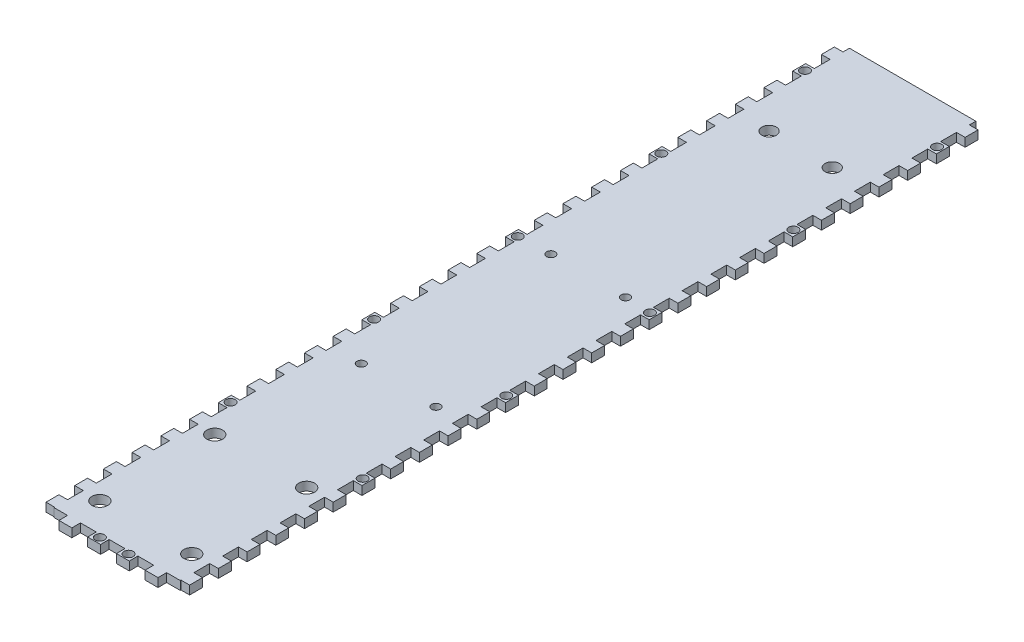
SolidWorks part; units mm, degrees
ref_plane "Plan de face" through (0, 0, 0) normal (0, 0, 1) x (1, 0, 0)
ref_plane "Plan de dessus" through (0, 0, 0) normal (0, 1, 0) x (1, 0, 0)
ref_plane "Plan de droite" through (0, 0, 0) normal (1, 0, 0) x (0, 0, -1)
sketch "Sketch1" plane through (0, 0, 0) normal (0, 0, 1) x (1, 0, 0)
  line L1 (-30.0201, 10.5217) -> (13.9799, 10.5217)
  line L2 (-30.0201, 10.5217) -> (-30.0201, 7.5217)
  line L3 (-30.0201, 7.5217) -> (13.9799, 7.5217)
  line L4 (13.9799, 10.5217) -> (13.9799, 7.5217)
  dimension "D1" = 44
  dimension "D2" = 3
extrude "Boss-Extrude1" add sketch "Sketch1" along normal blind 277
sketch "Sketch4" plane through (13.9799, 0, 0) normal (1, 0, 0) x (0, 0, -1)
  line L0 (-277, 10.5217) -> (0, 10.5217) construction
  line L1 (-276.75, 10.5217) -> (-272.25, 10.5217)
  line L2 (-276.75, 10.5217) -> (-276.75, 7.5217)
  line L3 (-276.75, 7.5217) -> (-272.25, 7.5217)
  line L4 (-272.25, 10.5217) -> (-272.25, 7.5217)
  line L5 (-277, 7.5217) -> (0, 7.5217) construction
  line L6 (-277, 7.5217) -> (-277, 10.5217) construction
  line L7 (-266.75, 10.5217) -> (-266.75, 7.5217)
  line L8 (-266.75, 10.5217) -> (-262.25, 10.5217)
  line L9 (-262.25, 10.5217) -> (-262.25, 7.5217)
  line L10 (-266.75, 7.5217) -> (-262.25, 7.5217)
  line L11 (-256.75, 10.5217) -> (-256.75, 7.5217)
  line L12 (-256.75, 10.5217) -> (-252.25, 10.5217)
  line L13 (-252.25, 10.5217) -> (-252.25, 7.5217)
  line L14 (-256.75, 7.5217) -> (-252.25, 7.5217)
  line L15 (-246.75, 10.5217) -> (-246.75, 7.5217)
  line L16 (-246.75, 10.5217) -> (-242.25, 10.5217)
  line L17 (-242.25, 10.5217) -> (-242.25, 7.5217)
  line L18 (-246.75, 7.5217) -> (-242.25, 7.5217)
  line L19 (-236.75, 10.5217) -> (-236.75, 7.5217)
  line L20 (-236.75, 10.5217) -> (-232.25, 10.5217)
  line L21 (-232.25, 10.5217) -> (-232.25, 7.5217)
  line L22 (-236.75, 7.5217) -> (-232.25, 7.5217)
  line L23 (-226.75, 10.5217) -> (-226.75, 7.5217)
  line L24 (-226.75, 10.5217) -> (-222.25, 10.5217)
  line L25 (-222.25, 10.5217) -> (-222.25, 7.5217)
  line L26 (-226.75, 7.5217) -> (-222.25, 7.5217)
  line L27 (-216.75, 10.5217) -> (-216.75, 7.5217)
  line L28 (-216.75, 10.5217) -> (-212.25, 10.5217)
  line L29 (-212.25, 10.5217) -> (-212.25, 7.5217)
  line L30 (-216.75, 7.5217) -> (-212.25, 7.5217)
  line L31 (-206.75, 10.5217) -> (-206.75, 7.5217)
  line L32 (-206.75, 10.5217) -> (-202.25, 10.5217)
  line L33 (-202.25, 10.5217) -> (-202.25, 7.5217)
  line L34 (-206.75, 7.5217) -> (-202.25, 7.5217)
  line L35 (-196.75, 10.5217) -> (-196.75, 7.5217)
  line L36 (-196.75, 10.5217) -> (-192.25, 10.5217)
  line L37 (-192.25, 10.5217) -> (-192.25, 7.5217)
  line L38 (-196.75, 7.5217) -> (-192.25, 7.5217)
  line L39 (-186.75, 10.5217) -> (-186.75, 7.5217)
  line L40 (-186.75, 10.5217) -> (-182.25, 10.5217)
  line L41 (-182.25, 10.5217) -> (-182.25, 7.5217)
  line L42 (-186.75, 7.5217) -> (-182.25, 7.5217)
  line L43 (-176.75, 10.5217) -> (-176.75, 7.5217)
  line L44 (-176.75, 10.5217) -> (-172.25, 10.5217)
  line L45 (-172.25, 10.5217) -> (-172.25, 7.5217)
  line L46 (-176.75, 7.5217) -> (-172.25, 7.5217)
  line L47 (-166.75, 10.5217) -> (-166.75, 7.5217)
  line L48 (-166.75, 10.5217) -> (-162.25, 10.5217)
  line L49 (-162.25, 10.5217) -> (-162.25, 7.5217)
  line L50 (-166.75, 7.5217) -> (-162.25, 7.5217)
  line L51 (-156.75, 10.5217) -> (-156.75, 7.5217)
  line L52 (-156.75, 10.5217) -> (-152.25, 10.5217)
  line L53 (-152.25, 10.5217) -> (-152.25, 7.5217)
  line L54 (-156.75, 7.5217) -> (-152.25, 7.5217)
  line L55 (-146.75, 10.5217) -> (-146.75, 7.5217)
  line L56 (-146.75, 10.5217) -> (-142.25, 10.5217)
  line L57 (-142.25, 10.5217) -> (-142.25, 7.5217)
  line L58 (-146.75, 7.5217) -> (-142.25, 7.5217)
  line L59 (-136.75, 10.5217) -> (-136.75, 7.5217)
  line L60 (-136.75, 10.5217) -> (-132.25, 10.5217)
  line L61 (-132.25, 10.5217) -> (-132.25, 7.5217)
  line L62 (-136.75, 7.5217) -> (-132.25, 7.5217)
  line L63 (-126.75, 10.5217) -> (-126.75, 7.5217)
  line L64 (-126.75, 10.5217) -> (-122.25, 10.5217)
  line L65 (-122.25, 10.5217) -> (-122.25, 7.5217)
  line L66 (-126.75, 7.5217) -> (-122.25, 7.5217)
  line L67 (-116.75, 10.5217) -> (-116.75, 7.5217)
  line L68 (-116.75, 10.5217) -> (-112.25, 10.5217)
  line L69 (-112.25, 10.5217) -> (-112.25, 7.5217)
  line L70 (-116.75, 7.5217) -> (-112.25, 7.5217)
  line L71 (-106.75, 10.5217) -> (-106.75, 7.5217)
  line L72 (-106.75, 10.5217) -> (-102.25, 10.5217)
  line L73 (-102.25, 10.5217) -> (-102.25, 7.5217)
  line L74 (-106.75, 7.5217) -> (-102.25, 7.5217)
  line L75 (-96.75, 10.5217) -> (-96.75, 7.5217)
  line L76 (-96.75, 10.5217) -> (-92.25, 10.5217)
  line L77 (-92.25, 10.5217) -> (-92.25, 7.5217)
  line L78 (-96.75, 7.5217) -> (-92.25, 7.5217)
  line L79 (-86.75, 10.5217) -> (-86.75, 7.5217)
  line L80 (-86.75, 10.5217) -> (-82.25, 10.5217)
  line L81 (-82.25, 10.5217) -> (-82.25, 7.5217)
  line L82 (-86.75, 7.5217) -> (-82.25, 7.5217)
  line L83 (-76.75, 10.5217) -> (-76.75, 7.5217)
  line L84 (-76.75, 10.5217) -> (-72.25, 10.5217)
  line L85 (-72.25, 10.5217) -> (-72.25, 7.5217)
  line L86 (-76.75, 7.5217) -> (-72.25, 7.5217)
  line L87 (-66.75, 10.5217) -> (-66.75, 7.5217)
  line L88 (-66.75, 10.5217) -> (-62.25, 10.5217)
  line L89 (-62.25, 10.5217) -> (-62.25, 7.5217)
  line L90 (-66.75, 7.5217) -> (-62.25, 7.5217)
  line L91 (-56.75, 10.5217) -> (-56.75, 7.5217)
  line L92 (-56.75, 10.5217) -> (-52.25, 10.5217)
  line L93 (-52.25, 10.5217) -> (-52.25, 7.5217)
  line L94 (-56.75, 7.5217) -> (-52.25, 7.5217)
  line L95 (-46.75, 10.5217) -> (-46.75, 7.5217)
  line L96 (-46.75, 10.5217) -> (-42.25, 10.5217)
  line L97 (-42.25, 10.5217) -> (-42.25, 7.5217)
  line L98 (-46.75, 7.5217) -> (-42.25, 7.5217)
  line L99 (-36.75, 10.5217) -> (-36.75, 7.5217)
  line L100 (-36.75, 10.5217) -> (-32.25, 10.5217)
  line L101 (-32.25, 10.5217) -> (-32.25, 7.5217)
  line L102 (-36.75, 7.5217) -> (-32.25, 7.5217)
  line L103 (-26.75, 10.5217) -> (-26.75, 7.5217)
  line L104 (-26.75, 10.5217) -> (-22.25, 10.5217)
  line L105 (-22.25, 10.5217) -> (-22.25, 7.5217)
  line L106 (-26.75, 7.5217) -> (-22.25, 7.5217)
  line L107 (-16.75, 10.5217) -> (-16.75, 7.5217)
  line L108 (-16.75, 10.5217) -> (-12.25, 10.5217)
  line L109 (-12.25, 10.5217) -> (-12.25, 7.5217)
  line L110 (-16.75, 7.5217) -> (-12.25, 7.5217)
  line L111 (-6.75, 10.5217) -> (-6.75, 7.5217)
  line L112 (-6.75, 10.5217) -> (-2.25, 10.5217)
  line L113 (-2.25, 10.5217) -> (-2.25, 7.5217)
  line L114 (-6.75, 7.5217) -> (-2.25, 7.5217)
  dimension "D1" = 0.25
  dimension "D2" = 4.5
  dimension "D3" = 28
extrude "Boss-Extrude2" add sketch "Sketch4" along normal blind 3
sketch "Sketch5" plane through (-30.0201, 0, 0) normal (-1, 0, 0) x (0, 0, 1)
  line L0 (277, 7.5217) -> (0, 7.5217) construction
  line L1 (276.75, 7.5217) -> (272.25, 7.5217)
  line L2 (276.75, 7.5217) -> (276.75, 10.5217)
  line L3 (276.75, 10.5217) -> (272.25, 10.5217)
  line L4 (272.25, 7.5217) -> (272.25, 10.5217)
  line L5 (277, 10.5217) -> (0, 10.5217) construction
  line L6 (277, 10.5217) -> (277, 7.5217) construction
  line L7 (266.75, 7.5217) -> (266.75, 10.5217)
  line L8 (266.75, 7.5217) -> (262.25, 7.5217)
  line L9 (262.25, 7.5217) -> (262.25, 10.5217)
  line L10 (266.75, 10.5217) -> (262.25, 10.5217)
  line L11 (256.75, 7.5217) -> (256.75, 10.5217)
  line L12 (256.75, 7.5217) -> (252.25, 7.5217)
  line L13 (252.25, 7.5217) -> (252.25, 10.5217)
  line L14 (256.75, 10.5217) -> (252.25, 10.5217)
  line L15 (246.75, 7.5217) -> (246.75, 10.5217)
  line L16 (246.75, 7.5217) -> (242.25, 7.5217)
  line L17 (242.25, 7.5217) -> (242.25, 10.5217)
  line L18 (246.75, 10.5217) -> (242.25, 10.5217)
  line L19 (236.75, 7.5217) -> (236.75, 10.5217)
  line L20 (236.75, 7.5217) -> (232.25, 7.5217)
  line L21 (232.25, 7.5217) -> (232.25, 10.5217)
  line L22 (236.75, 10.5217) -> (232.25, 10.5217)
  line L23 (226.75, 7.5217) -> (226.75, 10.5217)
  line L24 (226.75, 7.5217) -> (222.25, 7.5217)
  line L25 (222.25, 7.5217) -> (222.25, 10.5217)
  line L26 (226.75, 10.5217) -> (222.25, 10.5217)
  line L27 (216.75, 7.5217) -> (216.75, 10.5217)
  line L28 (216.75, 7.5217) -> (212.25, 7.5217)
  line L29 (212.25, 7.5217) -> (212.25, 10.5217)
  line L30 (216.75, 10.5217) -> (212.25, 10.5217)
  line L31 (206.75, 7.5217) -> (206.75, 10.5217)
  line L32 (206.75, 7.5217) -> (202.25, 7.5217)
  line L33 (202.25, 7.5217) -> (202.25, 10.5217)
  line L34 (206.75, 10.5217) -> (202.25, 10.5217)
  line L35 (196.75, 7.5217) -> (196.75, 10.5217)
  line L36 (196.75, 7.5217) -> (192.25, 7.5217)
  line L37 (192.25, 7.5217) -> (192.25, 10.5217)
  line L38 (196.75, 10.5217) -> (192.25, 10.5217)
  line L39 (186.75, 7.5217) -> (186.75, 10.5217)
  line L40 (186.75, 7.5217) -> (182.25, 7.5217)
  line L41 (182.25, 7.5217) -> (182.25, 10.5217)
  line L42 (186.75, 10.5217) -> (182.25, 10.5217)
  line L43 (176.75, 7.5217) -> (176.75, 10.5217)
  line L44 (176.75, 7.5217) -> (172.25, 7.5217)
  line L45 (172.25, 7.5217) -> (172.25, 10.5217)
  line L46 (176.75, 10.5217) -> (172.25, 10.5217)
  line L47 (166.75, 7.5217) -> (166.75, 10.5217)
  line L48 (166.75, 7.5217) -> (162.25, 7.5217)
  line L49 (162.25, 7.5217) -> (162.25, 10.5217)
  line L50 (166.75, 10.5217) -> (162.25, 10.5217)
  line L51 (156.75, 7.5217) -> (156.75, 10.5217)
  line L52 (156.75, 7.5217) -> (152.25, 7.5217)
  line L53 (152.25, 7.5217) -> (152.25, 10.5217)
  line L54 (156.75, 10.5217) -> (152.25, 10.5217)
  line L55 (146.75, 7.5217) -> (146.75, 10.5217)
  line L56 (146.75, 7.5217) -> (142.25, 7.5217)
  line L57 (142.25, 7.5217) -> (142.25, 10.5217)
  line L58 (146.75, 10.5217) -> (142.25, 10.5217)
  line L59 (136.75, 7.5217) -> (136.75, 10.5217)
  line L60 (136.75, 7.5217) -> (132.25, 7.5217)
  line L61 (132.25, 7.5217) -> (132.25, 10.5217)
  line L62 (136.75, 10.5217) -> (132.25, 10.5217)
  line L63 (126.75, 7.5217) -> (126.75, 10.5217)
  line L64 (126.75, 7.5217) -> (122.25, 7.5217)
  line L65 (122.25, 7.5217) -> (122.25, 10.5217)
  line L66 (126.75, 10.5217) -> (122.25, 10.5217)
  line L67 (116.75, 7.5217) -> (116.75, 10.5217)
  line L68 (116.75, 7.5217) -> (112.25, 7.5217)
  line L69 (112.25, 7.5217) -> (112.25, 10.5217)
  line L70 (116.75, 10.5217) -> (112.25, 10.5217)
  line L71 (106.75, 7.5217) -> (106.75, 10.5217)
  line L72 (106.75, 7.5217) -> (102.25, 7.5217)
  line L73 (102.25, 7.5217) -> (102.25, 10.5217)
  line L74 (106.75, 10.5217) -> (102.25, 10.5217)
  line L75 (96.75, 7.5217) -> (96.75, 10.5217)
  line L76 (96.75, 7.5217) -> (92.25, 7.5217)
  line L77 (92.25, 7.5217) -> (92.25, 10.5217)
  line L78 (96.75, 10.5217) -> (92.25, 10.5217)
  line L79 (86.75, 7.5217) -> (86.75, 10.5217)
  line L80 (86.75, 7.5217) -> (82.25, 7.5217)
  line L81 (82.25, 7.5217) -> (82.25, 10.5217)
  line L82 (86.75, 10.5217) -> (82.25, 10.5217)
  line L83 (76.75, 7.5217) -> (76.75, 10.5217)
  line L84 (76.75, 7.5217) -> (72.25, 7.5217)
  line L85 (72.25, 7.5217) -> (72.25, 10.5217)
  line L86 (76.75, 10.5217) -> (72.25, 10.5217)
  line L87 (66.75, 7.5217) -> (66.75, 10.5217)
  line L88 (66.75, 7.5217) -> (62.25, 7.5217)
  line L89 (62.25, 7.5217) -> (62.25, 10.5217)
  line L90 (66.75, 10.5217) -> (62.25, 10.5217)
  line L91 (56.75, 7.5217) -> (56.75, 10.5217)
  line L92 (56.75, 7.5217) -> (52.25, 7.5217)
  line L93 (52.25, 7.5217) -> (52.25, 10.5217)
  line L94 (56.75, 10.5217) -> (52.25, 10.5217)
  line L95 (46.75, 7.5217) -> (46.75, 10.5217)
  line L96 (46.75, 7.5217) -> (42.25, 7.5217)
  line L97 (42.25, 7.5217) -> (42.25, 10.5217)
  line L98 (46.75, 10.5217) -> (42.25, 10.5217)
  line L99 (36.75, 7.5217) -> (36.75, 10.5217)
  line L100 (36.75, 7.5217) -> (32.25, 7.5217)
  line L101 (32.25, 7.5217) -> (32.25, 10.5217)
  line L102 (36.75, 10.5217) -> (32.25, 10.5217)
  line L103 (26.75, 7.5217) -> (26.75, 10.5217)
  line L104 (26.75, 7.5217) -> (22.25, 7.5217)
  line L105 (22.25, 7.5217) -> (22.25, 10.5217)
  line L106 (26.75, 10.5217) -> (22.25, 10.5217)
  line L107 (16.75, 7.5217) -> (16.75, 10.5217)
  line L108 (16.75, 7.5217) -> (12.25, 7.5217)
  line L109 (12.25, 7.5217) -> (12.25, 10.5217)
  line L110 (16.75, 10.5217) -> (12.25, 10.5217)
  line L111 (6.75, 7.5217) -> (6.75, 10.5217)
  line L112 (6.75, 7.5217) -> (2.25, 7.5217)
  line L113 (2.25, 7.5217) -> (2.25, 10.5217)
  line L114 (6.75, 10.5217) -> (2.25, 10.5217)
  dimension "D1" = 0.25
  dimension "D2" = 4.5
  dimension "D3" = 28
extrude "Boss-Extrude3" add sketch "Sketch5" along normal blind 3
sketch "Sketch6" plane through (0, 0, 277) normal (0, 0, 1) x (1, 0, 0)
  line L0 (13.9799, 10.5217) -> (-30.0201, 10.5217) construction
  line L1 (-25.2701, 10.5217) -> (-20.7701, 10.5217)
  line L2 (-25.2701, 10.5217) -> (-25.2701, 7.5217)
  line L3 (-25.2701, 7.5217) -> (-20.7701, 7.5217)
  line L4 (-20.7701, 10.5217) -> (-20.7701, 7.5217)
  line L5 (-30.0201, 7.5217) -> (13.9799, 7.5217) construction
  line L6 (-30.0201, 7.5217) -> (-30.0201, 10.5217) construction
  line L7 (-15.2701, 10.5217) -> (-15.2701, 7.5217)
  line L8 (-15.2701, 10.5217) -> (-10.7701, 10.5217)
  line L9 (-10.7701, 10.5217) -> (-10.7701, 7.5217)
  line L10 (-15.2701, 7.5217) -> (-10.7701, 7.5217)
  line L11 (-5.2701, 10.5217) -> (-5.2701, 7.5217)
  line L12 (-5.2701, 10.5217) -> (-0.7701, 10.5217)
  line L13 (-0.7701, 10.5217) -> (-0.7701, 7.5217)
  line L14 (-5.2701, 7.5217) -> (-0.7701, 7.5217)
  line L15 (4.7299, 10.5217) -> (4.7299, 7.5217)
  line L16 (4.7299, 10.5217) -> (9.2299, 10.5217)
  line L17 (9.2299, 10.5217) -> (9.2299, 7.5217)
  line L18 (4.7299, 7.5217) -> (9.2299, 7.5217)
  dimension "D1" = 4.75
  dimension "D2" = 4.5
  dimension "D3" = 4
extrude "Boss-Extrude4" add sketch "Sketch6" along normal blind 3
sketch "Sketch7" plane through (0, 7.5217, 0) normal (0, -1, 0) x (1, 0, 0)
  line L0 (-8.0201, 277) -> (-8.0201, 0) construction
  line L1 (-10.7701, 277) -> (-5.2701, 277) construction
  line L2 (-30.0201, 0) -> (13.9799, 0) construction
  line L3 (13.9799, 276.75) -> (16.9799, 272.25) construction
  line L4 (16.9799, 266.75) -> (16.9799, 262.25) construction
  line L5 (16.9799, 276.75) -> (13.9799, 276.75) construction
  circle A0 centre (14.9799, 264.5) radius 1.6
  circle A1 centre (-31.0201, 264.5) radius 1.6
  circle A2 centre (-31.0201, 214.5) radius 1.6
  circle A3 centre (14.9799, 214.5) radius 1.6
  circle A4 centre (-31.0201, 164.5) radius 1.6
  circle A5 centre (14.9799, 164.5) radius 1.6
  circle A6 centre (-31.0201, 114.5) radius 1.6
  circle A7 centre (14.9799, 114.5) radius 1.6
  circle A8 centre (-31.0201, 64.5) radius 1.6
  circle A9 centre (14.9799, 64.5) radius 1.6
  circle A10 centre (-31.0201, 14.5) radius 1.6
  circle A11 centre (14.9799, 14.5) radius 1.6
  dimension "D1" = 6
  dimension "D3" = 3.2
  dimension "D4" = 2
  dimension "D2" = 12.25
extrude "Cut-Extrude1" cut sketch "Sketch7" against normal blind 3
sketch "Sketch8" plane through (0, 7.5217, 0) normal (0, -1, 0) x (1, 0, 0)
  line L0 (-8.0201, 0) -> (-8.0201, 54.5316) construction
  line L1 (-30.0201, 0) -> (13.9799, 0) construction
  circle A0 centre (-19.0201, 39) radius 2.5
  circle A1 centre (2.9799, 39) radius 2.5
  dimension "D1" = 5
  dimension "D2" = 11
  dimension "D3" = 39
extrude "Cut-Extrude2" cut sketch "Sketch8" against normal blind 12
sketch "Sketch9" plane through (0, 7.5217, 0) normal (0, -1, 0) x (-1, 0, 0)
  line L0 (15.2701, -280) -> (10.7701, -280) construction
  line L1 (5.2701, -280) -> (0.7701, -280) construction
  circle A0 centre (13.0201, -278) radius 1.6
  circle A1 centre (3.0201, -278) radius 1.6
  dimension "D1" = 3.2
  dimension "D2" = 3.2
  dimension "D3" = 2
  dimension "D4" = 2
extrude "Cut-Extrude3" cut sketch "Sketch9" against normal blind 12
sketch "Sketch11" plane through (0, 7.5217, 0) normal (0, -1, 0) x (1, 0, 0)
  line L0 (-10.7701, 277) -> (-5.2701, 277) construction
  circle A0 centre (-24.0201, 227) radius 2.75
  circle A1 centre (7.9799, 227) radius 2.75
  circle A2 centre (7.9799, 267) radius 2.75
  circle A3 centre (-24.0201, 267) radius 2.75
  point P10 (-8.0201, 277)
  dimension "D1" = 5.5
  dimension "D2" = 5.5
  dimension "D3" = 5.5
  dimension "D4" = 5.5
  dimension "D5" = 32
  dimension "D6" = 32
  dimension "D7" = 16
  dimension "D8" = 16
  dimension "D9" = 10
  dimension "D10" = 40
extrude "Cut-Extrude4" cut sketch "Sketch11" against normal through all both and the other way through all
extrude "Boss-Extrude5" add sketch "Sketch7<2>" against normal through all separate body contours A0 | A1 region at (14.9799, 7.5217, 264.5)
sketch "Sketch7<2>" plane through (0, 7.5217, 0) normal (0, -1, 0) x (1, 0, 0) same geometry as "Sketch7"
combine bodies "Combine1" operation type add bodies to combine 109 113 112
sketch "Sketch12" plane through (0, 7.5217, 0) normal (0, -1, 0) x (1, 0, 0)
  circle A0 centre (-19.8914, 114.1007) radius 1.5
  circle A1 centre (6.1086, 114.1007) radius 1.5
  circle A2 centre (-19.8914, 180.1007) radius 1.5
  circle A3 centre (6.1086, 180.1007) radius 1.5
  point P8 (-21.0622, 168.5499)
  point P9 (0, 0)
  point P10 (0, 0)
  point P11 (0, 0)
  point P12 (4.7938, 180.3074)
  point P13 (-16.7235, 165.9398)
  point P14 (0, 0)
  point P15 (-16.7235, 165.9398)
  point P16 (0, 0)
  point P17 (6.1086, 180.1007)
  dimension "D1" = 3
  dimension "D2" = 3
  dimension "D4" = 3
  dimension "D6" = 3
  dimension "D3" = 26
  dimension "D5" = 66
  dimension "D8" = 66
extrude "Cut-Extrude5" cut sketch "Sketch12" against normal through all both and the other way through all
